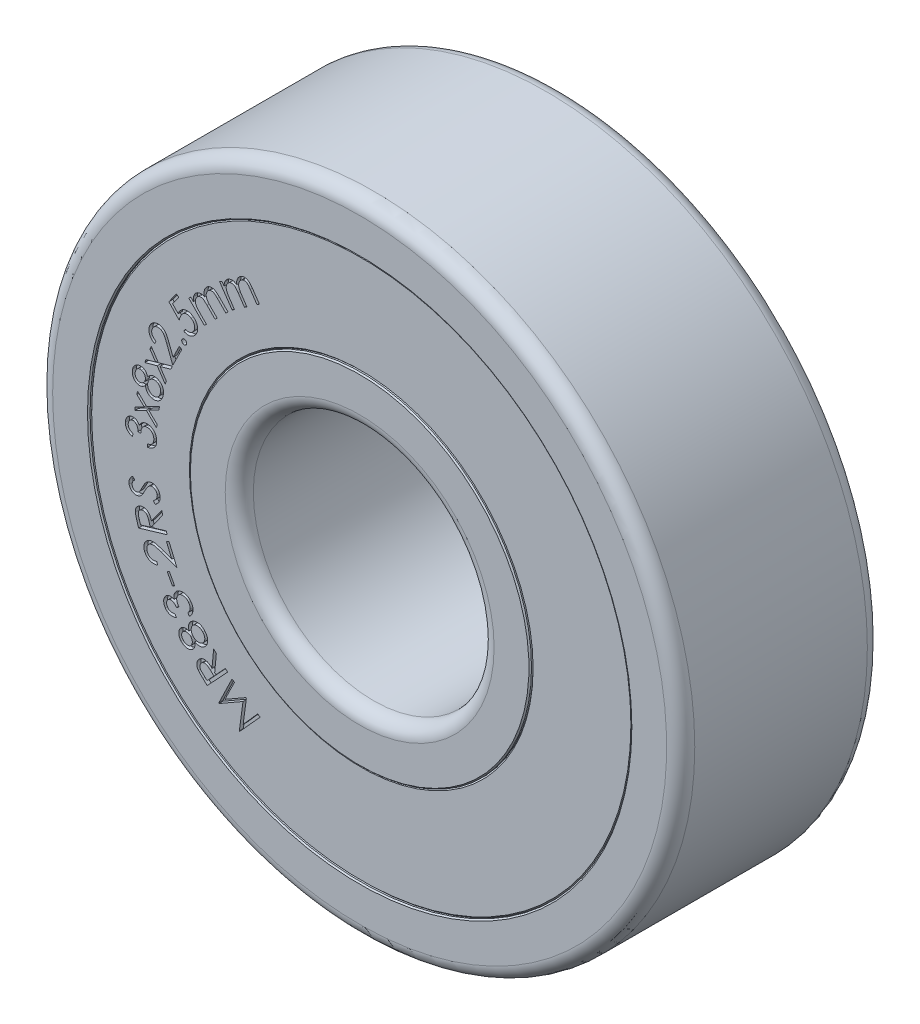
SolidWorks part; units mm, degrees
material "AISI 316 Annealed Stainless Steel Bar (SS)"
ref_plane "Front" through (0, 0, 0) normal (0, 0, 1) x (1, 0, 0)
ref_plane "Top" through (0, 0, 0) normal (0, 1, 0) x (1, 0, 0)
ref_plane "Right" through (0, 0, 0) normal (1, 0, 0) x (0, 0, -1)
sketch "LAYOUT R" plane through (0, 0, 0) normal (1, 0, 0) x (0, 0, -1)
  line L0 (-1.25, 1.5) -> (1.25, 1.5)
  line L1 (1.25, -4) -> (-1.25, -4) construction
  line L2 (1.25, -4) -> (1.25, 4) construction
  line L3 (1.25, 4) -> (-1.25, 4)
  line L4 (-1.25, -4) -> (-1.25, 4) construction
  line L5 (1.25, -4) -> (-1.25, 4) construction
  line L6 (1.25, 4) -> (-1.25, -4) construction
  line L7 (-1.25, 2.125) -> (1.25, 2.125)
  line L8 (-1.25, 3.375) -> (1.25, 3.375)
  line L11 (-17.5, 0) -> (17.5, 0) construction
  line L12 (-1.25, 4) -> (-1.25, 3.375)
  line L13 (1.25, 4) -> (1.25, 3.375)
  line L14 (-1.25, 3.375) -> (-1.25, 2.125)
  line L15 (1.25, 3.375) -> (1.25, 2.125)
  line L16 (-1.25, 2.125) -> (-1.25, 1.5)
  line L17 (1.25, 2.125) -> (1.25, 1.5)
  line L18 (-1.23, 3.375) -> (-1.23, 2.125)
  line L19 (1.23, 3.375) -> (1.23, 2.125)
  point P0 (0, 0)
  point P15 (0, 0)
  dimension "D1" = 2.5
  dimension "D2" = 8
  dimension "D3" = 1.5
  dimension "D6" = 0.02
  dimension "D7" = 0.02
  dimension "D4" = 2.125
  dimension "D5" = 3.375
sketch "Sketch R, INNER BODY" plane through (0, 0, 0) normal (1, 0, 0) x (0, 0, -1)
  line L0 (-1.25, 1.5) -> (1.25, 1.5) construction
  line L2 (-1.25, 2.125) -> (1.25, 2.125) construction
  line L4 (-1.25, 1.5) -> (1.25, 1.5)
  line L6 (-1.25, 2.125) -> (1.25, 2.125)
  line L8 (1.25, 2.125) -> (1.25, 1.5) construction
  line L9 (-1.25, 2.125) -> (-1.25, 1.5) construction
  line L10 (1.25, 2.125) -> (1.25, 1.5)
  line L11 (-1.25, 2.125) -> (-1.25, 1.5)
  line L12 (-17.5, 0) -> (17.5, 0) construction
  line L13 (-17.5, 0) -> (17.5, 0) construction
sketch "Sketch R, OUTER BODY" plane through (0, 0, 0) normal (1, 0, 0) x (0, 0, -1)
  line L2 (-1.25, 3.375) -> (1.25, 3.375) construction
  line L3 (1.25, 4) -> (-1.25, 4) construction
  line L6 (-1.25, 3.375) -> (1.25, 3.375)
  line L7 (1.25, 4) -> (-1.25, 4)
  line L8 (-17.5, 0) -> (17.5, 0) construction
  line L9 (-17.5, 0) -> (17.5, 0) construction
  line L10 (1.25, 4) -> (1.25, 3.375) construction
  line L11 (-1.25, 4) -> (-1.25, 3.375) construction
  line L12 (1.25, 4) -> (1.25, 3.375)
  line L13 (-1.25, 4) -> (-1.25, 3.375)
sketch "Sketch R, SEAL FACES" plane through (0, 0, 0) normal (1, 0, 0) x (0, 0, -1)
  line L0 (-17.5, 0) -> (17.5, 0) construction
  line L1 (-17.5, 0) -> (17.5, 0) construction
  line L3 (-1.25, 2.125) -> (1.25, 2.125) construction
  line L5 (-1.25, 3.375) -> (1.25, 3.375) construction
  line L7 (-1.23, 2.125) -> (1.23, 2.125)
  line L9 (-1.23, 3.375) -> (1.23, 3.375)
  line L10 (1.23, 3.375) -> (1.23, 2.125) construction
  line L11 (-1.23, 3.375) -> (-1.23, 2.125) construction
  line L12 (1.23, 3.375) -> (1.23, 2.125)
  line L13 (-1.23, 3.375) -> (-1.23, 2.125)
revolve "Revolve INNER BODY" add sketch "Sketch R, INNER BODY" angle 360 about L13
fillet "Fillet INNER BODY" radius 0.175 2 edges at (1.5, 0, 1.25) (1.5, 0, -1.25)
chamfer "Chamfer INNER BODY" distance 0.016 angle 45 2 edges at (2.125, 0, -1.25) (2.125, 0, 1.25)
revolve "Revolve OUTER BODY" add sketch "Sketch R, OUTER BODY" angle 360 about L9
fillet "Fillet OUTER BODY" radius 0.175 2 edges at (4, 0, -1.25) (4, 0, 1.25)
chamfer "Chamfer OUTER BODY" distance 0.016 angle 45 2 edges at (3.375, 0, 1.25) (3.375, 0, -1.25)
revolve "Revolve SEALS" add sketch "Sketch R, SEAL FACES" angle 360 about L1
chamfer "Chamfer SEALS" distance 0.016 angle 45 4 edges at (2.125, 0, -1.23) (3.375, 0, -1.23) (3.375, 0, 1.23) (2.125, 0, 1.23)
sketch "Sketch TEXT RADIUS 1 — MANUALLY ASSIGN TEXT AND FONT SIZE (FROM EQUATIONS)" plane through (0, 0, 1.23) normal (0, 0, 1) x (1, 0, 0)
  circle A0 centre (0, 0) radius 2.5625 construction
  text T0 "MR83-2RS  3x8x2.5mm" font "Century Gothic" height 0.375
  dimension "D1" = 5.125
extrude "Cut-Extrude SEAL LABEL 1" cut sketch "Sketch TEXT RADIUS 1 — MANUALLY ASSIGN TEXT AND FONT SIZE (FROM EQUATIONS)" against normal blind 0.05
sketch "Sketch TEXT RADIUS 2 — MANUALLY ASSIGN TEXT AND FONT SIZE (FROM EQUATIONS)" plane through (0, 0, -1.23) normal (0, 0, -1) x (-1, 0, 0)
  circle A0 centre (0, 0) radius 2.5625 construction
  text T0 "MR83-2RS  3x8x2.5mm" font "Century Gothic" height 0.375
  dimension "D1" = 5.125
extrude "Cut-Extrude SEAL LABEL 2" cut sketch "Sketch TEXT RADIUS 2 — MANUALLY ASSIGN TEXT AND FONT SIZE (FROM EQUATIONS)" against normal blind 0.05
equation "\"_i__BORE\"= 3"
equation "\"_i__OUTSIDE_DIAMETER\"= 8"
equation "\"_i__WIDTH\"= 2.5"
equation "\"_i_optional__TEXT_RADIUS_ADJUSTMENT\"= 0"
equation "\"_output__FONT_SIZE_mm\"= \"BODY_SPAN__SEAL__OF_RADIUS\" * \"param__FONT_SIZE_RATIO\"'MANUALLY ASSIGN TO FONT"
equation "\"BODY__HALF_WIDTH\"= \"_i__WIDTH\" / 2"
equation "\"BODY_SPAN___OF_DIAMETER\"= \"_i__OUTSIDE_DIAMETER\" - \"_i__BORE\""
equation "\"BODY_SPAN___OF_RADIUS\"= \"BODY_SPAN___OF_DIAMETER\" / 2"
equation "\"BODY_SPAN__BORE_AND_OD__OF RADIUS\"= ( \"BODY_SPAN___OF_RADIUS\" - \"BODY_SPAN__SEAL__OF_RADIUS\" ) / 2"
equation "\"BODY_SPAN__SEAL__OF_RADIUS\"= \"BODY_SPAN___OF_RADIUS\" * \"param__SEAL_PANEL_SPAN__RATIO_OF_BODY_RADIAN\""
equation "\"BORE__RADIUS\"= \"_i__BORE\" / 2"
equation "\"CORNER_RADII\"= \"_i__WIDTH\" * \"param__CORNER_RADII__ISO_MAX_RATIO_TO_WIDTH\""
equation "\"param__CORNER_RADII__ISO_MAX_RATIO_TO_WIDTH\"= 0.07'WHERE WIDTH IS LESS THAN DIAMETER"
equation "\"param__FONT_SIZE_RATIO\"= 0.3"
equation "\"param__SEAL_FACE_INSET__RATIO_OF_WIDTH\"= .01"
equation "\"param__SEAL_PANEL_SPAN__RATIO_OF_BODY_RADIAN\"= 0.5"
equation "\"param__SIDE_CHAMFERS__RATIO_TO_OD\"= 1 / 500"
equation "\"RING_INNER__OUTSIDE_RADIUS\"= \"BORE__RADIUS\" + \"BODY_SPAN__BORE_AND_OD__OF RADIUS\""
equation "\"RING_OUTER__OUTSIDE_RADIUS\"= ( \"_i__OUTSIDE_DIAMETER\" / 2 ) - \"BODY_SPAN__BORE_AND_OD__OF RADIUS\""
equation "\"SEAL_FACE_INSET\"= \"_i__WIDTH\" * \"param__SEAL_FACE_INSET__RATIO_OF_WIDTH\""
equation "\"SIDE_FACE_AND_SEAL_CHAMFERS\"= \"_i__OUTSIDE_DIAMETER\" * \"param__SIDE_CHAMFERS__RATIO_TO_OD\""
equation "\"TEXT_RADIUS\"= \"_i__BORE\" + ( \"BODY_SPAN___OF_DIAMETER\" / 2 ) - \"_output__FONT_SIZE_mm\" + \"_i_optional__TEXT_RADIUS_ADJUSTMENT\""
equation "\"D1@Chamfer INNER BODY\"=\"SIDE_FACE_AND_SEAL_CHAMFERS\""
equation "\"D1@Chamfer OUTER BODY\"=\"SIDE_FACE_AND_SEAL_CHAMFERS\""
equation "\"D1@Chamfer SEALS\"=\"SIDE_FACE_AND_SEAL_CHAMFERS\""
equation "\"D1@Fillet INNER BODY\"=\"CORNER_RADII\""
equation "\"D1@Fillet OUTER BODY\"=\"CORNER_RADII\""
equation "\"D1@LAYOUT R\"=\"_i__WIDTH\""
equation "\"D1@Sketch TEXT RADIUS 1 — MANUALLY ASSIGN TEXT AND FONT SIZE (FROM EQUATIONS)\" = \"TEXT_RADIUS\""
equation "\"D1@Sketch TEXT RADIUS 2 — MANUALLY ASSIGN TEXT AND FONT SIZE (FROM EQUATIONS)\" = \"TEXT_RADIUS\""
equation "\"D2@LAYOUT R\"=\"_i__OUTSIDE_DIAMETER\""
equation "\"D3@LAYOUT R\"=\"BORE__RADIUS\""
equation "\"D4@LAYOUT R\"=\"RING_INNER__OUTSIDE_RADIUS\""
equation "\"D5@LAYOUT R\"=\"RING_OUTER__OUTSIDE_RADIUS\""
